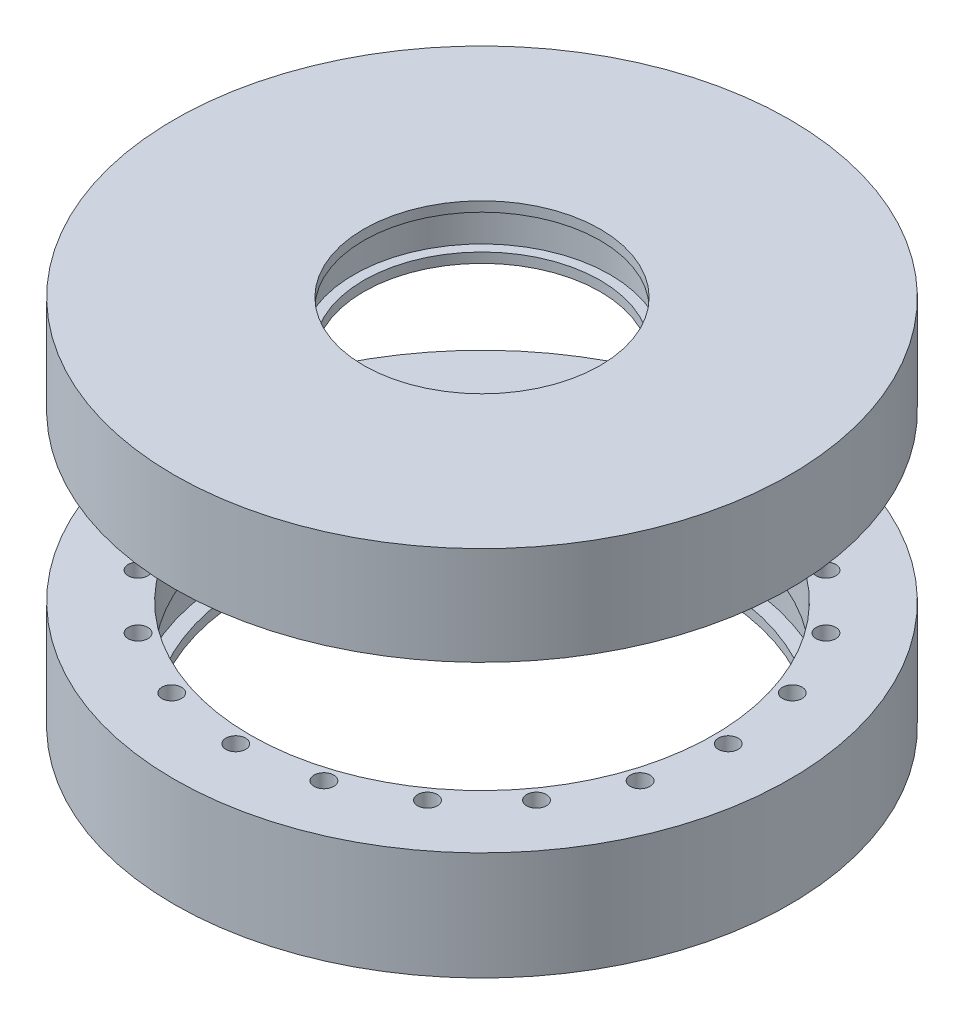
SolidWorks part; units mm, degrees
ref_plane "Front Plane" through (0, 0, 0) normal (0, 0, 1) x (1, 0, 0)
ref_plane "Top Plane" through (0, 0, 0) normal (0, 1, 0) x (1, 0, 0)
ref_plane "Right Plane" through (0, 0, 0) normal (1, 0, 0) x (0, 0, -1)
ref_axis "Axis1" through (0, -41.525, 0) along (0, 1, 0)
sketch "Sketch2" plane through (0, 0, 0) normal (1, 0, 0) x (0, 0, -1)
  line L0 (47, -37.75) -> (62.5, -37.75)
  line L1 (62.5, -37.75) -> (62.5, 37.75)
  line L2 (62.5, 37.75) -> (24, 37.75)
  line L3 (24, 37.75) -> (24, 35.75)
  line L4 (24, 35.75) -> (26, 35.75)
  line L5 (26, 35.75) -> (26, 28.75)
  line L6 (26, 28.75) -> (24, 28.75)
  line L7 (24, 28.75) -> (24, 26.75)
  line L8 (24, 26.75) -> (42.5, 26.75)
  line L11 (47, -25.75) -> (50, -25.75)
  line L12 (50, -25.75) -> (50, -35.75)
  line L13 (50, -35.75) -> (47, -35.75)
  line L14 (47, -35.75) -> (47, -37.75)
  line L15 (47, -25.75) -> (47, -15.75)
  line L17 (53, -15.75) -> (53, 17.75)
  line L18 (0, -15.4373) -> (0, -9.583) construction
  line L19 (0, 0) -> (62.5, 0) construction
  line L20 (47, -15.75) -> (53, -15.75)
  line L21 (42.5, 26.75) -> (42.5, 17.75)
  line L22 (42.5, 17.75) -> (53, 17.75)
  dimension "D1" = 10
  dimension "D2" = 7
  dimension "D3" = 2
  dimension "D4" = 100
  dimension "D5" = 52
  dimension "D6" = 71.5
  dimension "D7" = 125
  dimension "D8" = 2
  dimension "D9" = 3
  dimension "D10" = 106
  dimension "D11" = 10
  dimension "D12" = 85
  dimension "D13" = 20
revolve "Revolve1" add sketch "Sketch2" angle 360 about L18
sketch "Sketch3" plane through (0, -25.75, 0) normal (0, -1, 0) x (1, 0, 0)
  line L0 (-47.5528, 15.4508) -> (0, 0) construction
  line L1 (0, 0) -> (-50, 0) construction
  circle A0 centre (0, 0) radius 50 construction
  circle A1 centre (-47.5528, 15.4508) radius 2
  circle A2 centre (-40.4508, 29.3893) radius 2
  circle A3 centre (-29.3893, 40.4508) radius 2
  circle A4 centre (-15.4508, 47.5528) radius 2
  circle A5 centre (0, 50) radius 2
  circle A6 centre (15.4508, 47.5528) radius 2
  circle A7 centre (29.3893, 40.4508) radius 2
  circle A8 centre (40.4508, 29.3893) radius 2
  circle A9 centre (47.5528, 15.4508) radius 2
  circle A10 centre (50, 0) radius 2
  circle A11 centre (47.5528, -15.4508) radius 2
  circle A12 centre (40.4508, -29.3893) radius 2
  circle A13 centre (29.3893, -40.4508) radius 2
  circle A14 centre (15.4508, -47.5528) radius 2
  circle A15 centre (0, -50) radius 2
  circle A16 centre (-15.4508, -47.5528) radius 2
  circle A17 centre (-29.3893, -40.4508) radius 2
  circle A18 centre (-40.4508, -29.3893) radius 2
  circle A19 centre (-47.5528, -15.4508) radius 2
  circle A20 centre (-50, 0) radius 2
  point P45 (0, 0)
  dimension "D1" = 4
  dimension "D2" = 100
  dimension "D4" = 18
  dimension "D3" = 20
extrude "Cut-Extrude5" cut sketch "Sketch3" against normal blind 50 from offset 2.5 offset against normal yes
sketch "Sketch5" plane through (0, -15.75, 0) normal (0, 1, 0) x (1, 0, 0)
  circle A0 centre (0, 0) radius 62.5
  circle A1 centre (0, 0) radius 62.5 construction
extrude "Cut-Extrude6" cut sketch "Sketch5" along normal up to surface (33.5 mm away) up to face at (-40.4508, 17.75, 27.3893)
ref_plane "Plane3" through (0, 0, 62.5) normal (0, 0, 1) x (1, 0, 0)
